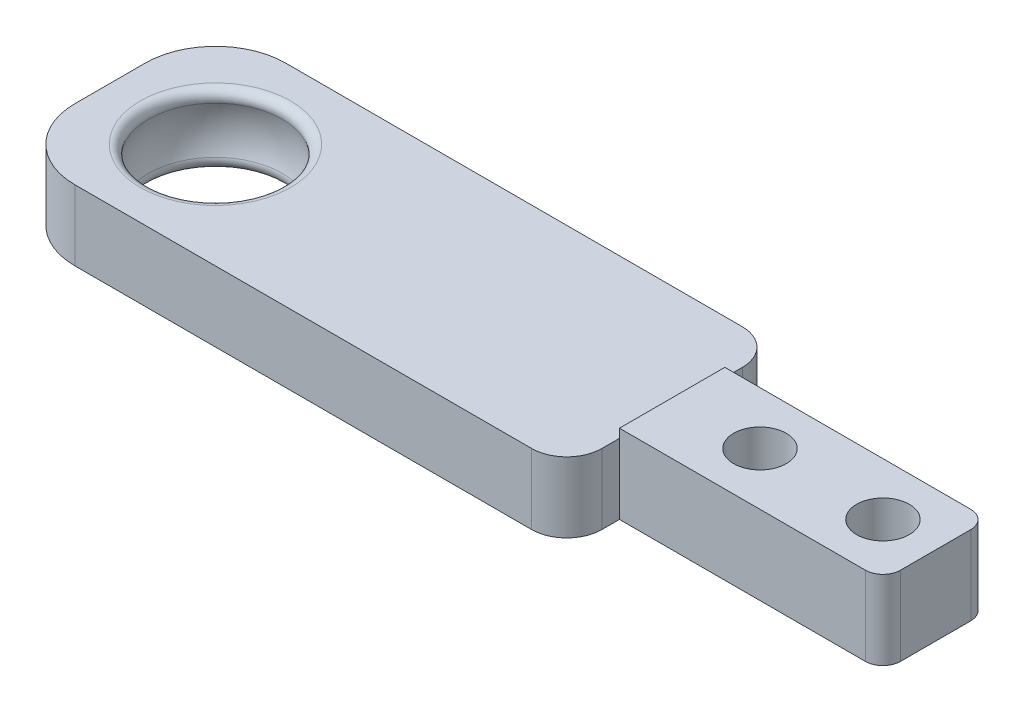
SolidWorks part; units mm, degrees
ref_plane "Front Plane" through (0, 0, 0) normal (0, 0, 1) x (1, 0, 0)
ref_plane "Top Plane" through (0, 0, 0) normal (0, 1, 0) x (1, 0, 0)
ref_plane "Right Plane" through (0, 0, 0) normal (1, 0, 0) x (0, 0, -1)
sketch "Sketch1" plane through (0, 0, 0) normal (0, 1, 0) x (1, 0, 0)
  line L1 (16, 6) -> (-16, 6)
  line L2 (16, 6) -> (16, -6)
  line L3 (16, -6) -> (-16, -6)
  line L4 (-16, 6) -> (-16, -6)
  line L5 (16, 6) -> (-16, -6) construction
  line L6 (16, -6) -> (-16, 6) construction
  point P0 (0, 0)
  dimension "D1" = 32
  dimension "D2" = 12
extrude "Boss-Extrude1" add sketch "Sketch1" along normal blind 4
sketch "Sketch2" plane through (0, 0, 0) normal (0, 0, 1) x (1, 0, 0)
  line L0 (-10, 4) -> (-10, 0)
  line L1 (-16, 4) -> (16, 4) construction
  line L2 (-16, 0) -> (16, 0) construction
  line L3 (-16, 4) -> (-16, 0) construction
  line L4 (-10, 4) -> (-13.5, 4)
  line L5 (-13.5, 0) -> (-10, 0)
  arc A0 (-13.5, 4) -> (-13.5, 0) centre (-10, 2) ccw
  dimension "D1" = 6
  dimension "D2" = 3.5
revolve "Cut-Revolve1" cut sketch "Sketch2" angle 360 about L0
fillet "Fillet1" radius 4 2 edges at (-16, 2, -6) (-16, 2, 6)
fillet "Fillet2" radius 0.5 2 edges at (-13.5, 4, 0) (-13.5, 0, 0)
sketch "Sketch3" plane through (16, 0, 0) normal (1, 0, 0) x (0, 0, -1)
  line L0 (-6, 4) -> (6, 4) construction
  line L1 (-6, 0) -> (6, 0) construction
  line L2 (-3, 4) -> (3, 4)
  line L3 (-3, 4) -> (-3, 0)
  line L4 (-3, 0) -> (3, 0)
  line L5 (3, 4) -> (3, 0)
  dimension "D1" = 6
  dimension "D2" = 3
extrude "Boss-Extrude2" add sketch "Sketch3" along normal blind 15
sketch "Sketch5" plane through (0, 4, 0) normal (0, 1, 0) x (1, 0, 0)
  line L1 (16, 3) -> (16, 6) construction
  circle A0 centre (21, 0) radius 1.5
  circle A1 centre (28, 0) radius 1.5
  dimension "D1" = 3
  dimension "D2" = 3
  dimension "D3" = 7
  dimension "D4" = 5
extrude "Cut-Extrude1" cut sketch "Sketch5" against normal through all
sketch "Sketch6" plane through (0, 4, 0) normal (0, 1, 0) x (1, 0, 0)
  line L1 (31, 3) -> (16, 3)
  line L2 (31, 3) -> (31, -3)
  line L3 (31, -3) -> (16, -3)
  line L4 (16, 3) -> (16, -3)
  circle A0 centre (21, 0) radius 1.5
  circle A1 centre (28, 0) radius 1.5
extrude "Boss-Extrude3" add sketch "Sketch6" along normal blind 0.5
fillet "Fillet3" radius 2 2 edges at (16, 2, 6) (16, 2, -6)
fillet "Fillet4" radius 1 2 edges at (31, 2.25, 3) (31, 2.25, -3)
